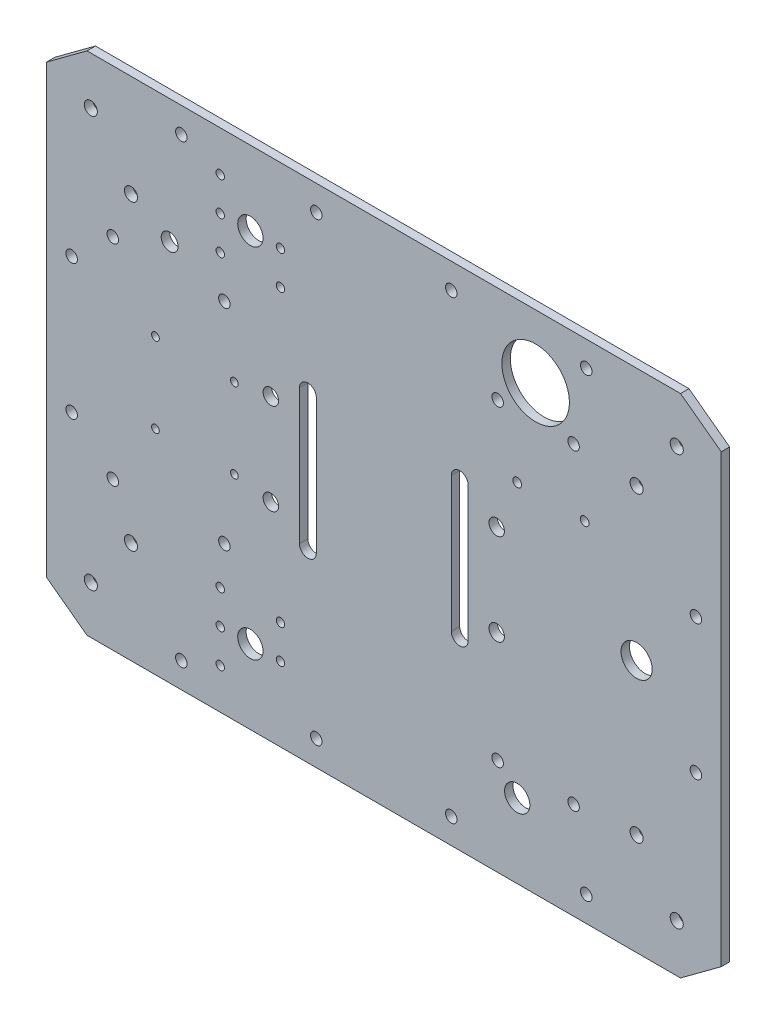
SolidWorks part; units mm, degrees
material "Thornel Mat VMA"
ref_plane "Front Plane" through (0, 0, 0) normal (0, 0, 1) x (1, 0, 0)
ref_plane "Top Plane" through (0, 0, 0) normal (0, 1, 0) x (1, 0, 0)
ref_plane "Right Plane" through (0, 0, 0) normal (1, 0, 0) x (0, 0, -1)
sketch "Sketch1" plane through (0, 0, 0) normal (0, 0, 1) x (1, 0, 0)
  line L0 (-127, 0) -> (127, 0) construction
  line L1 (0, -95.25) -> (0, 95.25) construction
  line L2 (-107.95, 0) -> (-107.95, 41.011) construction
  line L3 (-107.95, 41.011) -> (-95.25, 41.011) construction
  line L4 (-95.25, 41.011) -> (-79.9365, 52.3423) construction
  line L5 (-79.9365, 52.3423) -> (-79.9365, 76.2) construction
  line L6 (-79.9365, 76.2) -> (0, 76.2) construction
  line L7 (-95.25, 41.011) -> (-127, 83.9186) construction
  line L8 (-79.9365, 52.3423) -> (-111.6865, 95.25) construction
  line L9 (-111.6865, -95.25) -> (-127, -83.9186)
  line L10 (111.6865, -95.25) -> (127, -83.9186)
  line L11 (111.6865, 95.25) -> (127, 83.9186)
  line L12 (-87.5933, 46.6767) -> (-95.1475, 56.8856) construction
  line L13 (-95.1475, 56.8856) -> (-110.256, 77.3036) construction
  line L24 (127, -83.9186) -> (127, 83.9186)
  line L26 (111.6865, 95.25) -> (-111.6865, 95.25)
  line L27 (-111.6865, 95.25) -> (-127, 83.9186)
  line L28 (-127, 83.9186) -> (-127, -83.9186)
  line L30 (-111.6865, -95.25) -> (111.6865, -95.25)
  circle A0 centre (-95.1475, 56.8856) radius 2.4638
  circle A1 centre (-110.256, 77.3036) radius 2.4638
  circle A2 centre (110.256, 77.3036) radius 2.4638
  circle A3 centre (95.1475, 56.8856) radius 2.4638
  circle A4 centre (-110.256, -77.3036) radius 2.4638
  circle A5 centre (-95.1475, -56.8856) radius 2.4638
  circle A6 centre (110.256, -77.3036) radius 2.4638
  circle A7 centre (95.1475, -56.8856) radius 2.4638
  circle A8 centre (95.1475, 0) radius 5.855
  point P12 (0, 0)
  dimension "D10" = 11.71
  dimension "D1" = 190.5
  dimension "D2" = 254
  dimension "D3" = 19.05
  dimension "D4" = 19.05
  dimension "D5" = 12.7
  dimension "D6" = 19.05
  dimension "D7" = 143.5
  dimension "D8" = 12.7
  dimension "D9" = 25.4
extrude "Boss-Extrude1" add sketch "Sketch1" along normal blind 3.175
sketch "Sketch2" plane through (0, 0, 3.175) normal (0, 0, 1) x (1, 0, 0)
  line L0 (-127, 0) -> (127, 0) construction
  line L1 (-127, 83.9186) -> (-127, -83.9186) construction
  line L2 (127, -83.9186) -> (127, 83.9186) construction
  line L3 (57.15, 65.0875) -> (57.15, -65.0875) construction
  line L4 (38.1, 65.0875) -> (76.2, 65.0875)
  line L5 (38.1, 65.0875) -> (38.1, -65.0875)
  line L6 (38.1, -65.0875) -> (76.2, -65.0875)
  line L7 (76.2, 65.0875) -> (76.2, -65.0875)
  line L8 (38.1, 65.0875) -> (76.2, -65.0875) construction
  line L9 (38.1, -65.0875) -> (76.2, 65.0875) construction
  line L10 (57.15, 58.7375) -> (47.625, 58.7375) construction
  line L11 (47.625, 58.7375) -> (38.1, 58.7375) construction
  circle A0 centre (42.8625, 58.7375) radius 2.159
  circle A1 centre (42.8625, -58.7375) radius 2.159
  circle A2 centre (71.4375, -58.7375) radius 2.159
  circle A3 centre (71.4375, 58.7375) radius 2.159
  point P6 (57.15, 0)
  point P17 (42.8625, 58.7375)
  dimension "D1" = 38.1
  dimension "D2" = 130.175
  dimension "D3" = 6.35
  dimension "D4" = 9.525
  dimension "D5" = 69.85
extrude "Cut-Extrude1" cut sketch "Sketch2" against normal through all contours A1 | A2 | A3 | A0 region at (42.8625, 58.7375, 3.175) region at (42.8625, -58.7375, 3.175) region at (71.4375, -58.7375, 3.175) region at (71.4375, 58.7375, 3.175)
sketch "Sketch3" plane through (0, 0, 3.175) normal (0, 0, 1) x (1, 0, 0)
  line L0 (0, 95.25) -> (0, -95.25) construction
  line L1 (111.6865, 95.25) -> (-111.6865, 95.25) construction
  line L2 (-111.6865, -95.25) -> (111.6865, -95.25) construction
  line L3 (127, 0) -> (-127, 0) construction
  line L4 (127, -83.9186) -> (127, 83.9186) construction
  line L5 (-127, 83.9186) -> (-127, -83.9186) construction
  line L8 (119.3433, -89.5843) -> (111.789, -79.3753) construction
  line L10 (111.6865, -95.25) -> (127, -83.9186) construction
  line L11 (111.6865, -95.25) -> (127, -83.9186)
  circle A0 centre (111.789, -79.3753) radius 1.9844
  circle A1 centre (96.6805, -58.9574) radius 1.9844
  dimension "D2" = 3.9688
  dimension "D3" = 3.9688
  dimension "D1" = 12.7
  dimension "D4" = 25.4
sketch "Sketch5" plane through (0, 0, 0) normal (0, 0, -1) x (-1, 0, 0)
  line L0 (-127, 0) -> (127, 0) construction
  line L1 (105.9946, 43.5) -> (55.9947, 43.5) construction
  line L2 (105.9946, 43.5) -> (105.9946, -43.5) construction
  line L3 (105.9946, -43.5) -> (55.9947, -43.5) construction
  line L4 (55.9947, 43.5) -> (55.9947, -43.5) construction
  line L5 (89.2369, 18.0341) -> (89.2369, -18.0339)
  line L6 (67.8946, 95.25) -> (67.8946, -95.25) construction
  line L7 (-71.4375, 58.7375) -> (-42.8625, 58.7375) construction
  line L8 (0, 64.0679) -> (0, -49.8393) construction
  line L9 (-42.5, 17.2) -> (42.5, 17.2) construction
  line L10 (-42.5, 17.2) -> (-42.5, -17.2) construction
  line L11 (-42.5, -17.2) -> (42.5, -17.2) construction
  line L12 (42.5, 17.2) -> (42.5, -17.2) construction
  line L13 (-42.5, 17.2) -> (42.5, -17.2) construction
  line L14 (-42.5, -17.2) -> (42.5, 17.2) construction
  line L15 (80.5946, 60.96) -> (31.75, 60.96) construction
  line L16 (61.5446, -67.31) -> (-87.4336, -67.31) construction
  line L17 (50.2154, -67.31) -> (50.2154, 67.31) construction
  line L18 (50.2154, 67.31) -> (38.8861, 67.31) construction
  line L19 (-28.575, 25.4) -> (-28.575, -25.4) construction
  line L20 (-111.6865, 95.25) -> (111.6865, 95.25) construction
  line L21 (-127, -83.9186) -> (-127, 83.9186) construction
  line L22 (-57.15, 71.4375) -> (80.5946, 71.4375) construction
  line L23 (80.5946, 71.4375) -> (80.5946, 48.58) construction
  line L25 (80.5946, -77.0458) -> (80.5946, 48.58) construction
  line L26 (127, 0) -> (-127, 0) construction
  line L27 (80.9947, 0) -> (80.9947, -8419.0368) construction
  line L28 (-25.4, 25.4) -> (-25.4, -25.4)
  line L29 (-31.75, 25.4) -> (-31.75, -25.4)
  line L30 (28.575, 25.4) -> (28.575, -25.4) construction
  line L31 (25.4, 25.4) -> (25.4, -25.4)
  line L32 (31.75, 25.4) -> (31.75, -25.4)
  line L33 (71.0787, 0) -> (71.0787, 12.3782) construction
  line L34 (53.2197, 18.0341) -> (89.2369, 18.0341)
  line L35 (53.2197, 18.0341) -> (53.2197, -18.0339)
  line L36 (53.2197, -18.0339) -> (89.2369, -18.0339)
  line L40 (-57.15, 58.7375) -> (-57.15, 95.25) construction
  circle A0 centre (61.5446, -54.61) radius 1.5875
  circle A1 centre (61.5446, -67.31) radius 1.5875
  circle A2 centre (80.5946, 48.58) radius 3.175
  circle A3 centre (-57.15, 71.4375) radius 12.7
  circle A4 centre (61.5446, 54.61) radius 1.5875
  circle A5 centre (61.5446, -80.01) radius 1.5875
  circle A6 centre (-50.2154, -67.31) radius 4.7625
  circle A7 centre (50.2154, -67.31) radius 4.7625
  circle A8 centre (61.5446, 67.31) radius 1.5875
  circle A9 centre (61.5446, 80.01) radius 1.5875
  circle A10 centre (50.2154, 67.31) radius 4.7625
  circle A11 centre (-50.2154, 35.56) radius 1.651
  circle A12 centre (59.9952, 39.4995) radius 2.159
  circle A13 centre (101.9941, 39.4995) radius 2.159
  circle A14 centre (59.9952, -39.4995) radius 2.159
  circle A15 centre (101.9941, -39.4995) radius 2.159
  circle A16 centre (38.8861, 67.31) radius 1.5875
  circle A17 centre (38.8861, 54.61) radius 1.5875
  circle A18 centre (38.8861, -67.31) radius 1.5875
  circle A19 centre (38.8861, -54.61) radius 1.5875
  arc A20 (-25.4, 25.4) -> (-31.75, 25.4) centre (-28.575, 25.4) ccw
  arc A21 (-31.75, -25.4) -> (-25.4, -25.4) centre (-28.575, -25.4) ccw
  arc A22 (25.4, 25.4) -> (31.75, 25.4) centre (28.575, 25.4) cw
  arc A23 (31.75, -25.4) -> (25.4, -25.4) centre (28.575, -25.4) cw
  circle A24 centre (56.2197, 15.0341) radius 1.4478
  circle A25 centre (56.2197, -15.0341) radius 1.4478
  circle A26 centre (85.9377, -15.0341) radius 1.4478
  circle A27 centre (85.9377, 15.0341) radius 1.4478
  circle A28 centre (-42.5, 17.2) radius 2.9083
  circle A29 centre (-42.5, -17.2) radius 2.9083
  circle A30 centre (42.5, -17.2) radius 2.9083
  circle A31 centre (42.5, 17.2) radius 2.9083
  circle A32 centre (-75.6154, 35.6276) radius 1.651
  point P0 (80.9947, 0)
  point P9 (0, 0)
  point P77 (-28.575, 0)
  point P84 (28.575, 0)
  point P89 (71.0787, 0)
  point P112 (0, 0)
  dimension "D10" = 6.35
  dimension "D15" = 2.9997
  dimension "D17" = 3.302
  dimension "D18" = 3.302
  dimension "D25" = 4.0005
  dimension "D45" = 2.8956
  dimension "D9" = 59.69
  dimension "D13" = 14.859
  dimension "D14" = 3
  dimension "D8" = 111.76
  dimension "D1" = 87.0001
  dimension "D2" = 49.9999
  dimension "D4" = 34.4
  dimension "D5" = 85
  dimension "D6" = 6.35
  dimension "D7" = 12.7
  dimension "D11" = 5.08
  dimension "D12" = 25.4
  dimension "D16" = 25.4
  dimension "D26" = 4.0005
  dimension "D38" = 50.8
  dimension "D39" = 6.35
  dimension "D40" = 28.575
  dimension "D41" = 36.0172
  dimension "D42" = 36.068
  dimension "D44" = 3
extrude "Cut-Extrude2" cut sketch "Sketch5" against normal through all contours A3 | A2 | A14 | A15 | A13 | A12 | L29 A21 L28 A20 | A23 L4 A22 L31 | A23 L32 A22 L4 | A27 | A24 | A25 | A26
sketch "Sketch6" plane through (0, 0, 0) normal (0, 0, -1) x (-1, 0, 0)
  line L0 (0, 0) -> (-135.1326, 0) construction
  line L1 (0, 0) -> (0, -95.25) construction
  line L2 (111.6865, -95.25) -> (-111.6865, -95.25) construction
  line L3 (-76.2, -95.25) -> (-76.2, -85.725) construction
  line L4 (117.475, 0) -> (117.475, -25.4) construction
  line L5 (127, 0) -> (-127, 0) construction
  line L6 (127, 83.9186) -> (127, -83.9186) construction
  circle A0 centre (-76.2, -85.725) radius 2.159
  circle A1 centre (-25.4, -85.725) radius 2.159
  circle A2 centre (25.4, -85.725) radius 2.159
  circle A3 centre (76.2, -85.725) radius 2.159
  circle A4 centre (76.2, 85.725) radius 2.159
  circle A5 centre (25.4, 85.725) radius 2.159
  circle A6 centre (-25.4, 85.725) radius 2.159
  circle A7 centre (-76.2, 85.725) radius 2.159
  circle A8 centre (117.475, -25.4) radius 2.159
  circle A9 centre (117.475, 25.4) radius 2.159
  circle A10 centre (-117.475, 25.4) radius 2.159
  circle A11 centre (-117.475, -25.4) radius 2.159
  dimension "D2" = 9.525
  dimension "D3" = 76.2
  dimension "D5" = 9.525
  dimension "D6" = 25.4
  dimension "D4" = 4
extrude "Cut-Extrude3" cut sketch "Sketch6" against normal through all
extrude "Cut-Extrude4" cut sketch "Sketch5<3>" against normal through all contours A28 | A29 | A31 | A30
sketch "Sketch5<3>" plane through (0, 0, 0) normal (0, 0, -1) x (-1, 0, 0) same geometry as "Sketch5"
extrude "Cut-Extrude5" cut sketch "Sketch5<4>" against normal through all contours A10 | A9 | A8 | A4 | A0 | A1 | A5 | A7 | A6
sketch "Sketch5<4>" plane through (0, 0, 0) normal (0, 0, -1) x (-1, 0, 0) same geometry as "Sketch5"
extrude "Cut-Extrude6" cut sketch "Sketch5<5>" against normal blind 2.54 contours A18 | A17 | A16
sketch "Sketch5<5>" plane through (0, 0, 0) normal (0, 0, -1) x (-1, 0, 0) same geometry as "Sketch5"
extrude "Cut-Extrude7" cut sketch "Sketch5<6>" against normal through all contours A17 | A18 | A16
sketch "Sketch5<6>" plane through (0, 0, 0) normal (0, 0, -1) x (-1, 0, 0) same geometry as "Sketch5"
sketch "Sketch8" plane through (0, 0, 3.175) normal (0, 0, 1) x (1, 0, 0)
extrude "Cut-Extrude8" cut sketch "Sketch5<7>" against normal blind 2.54 contours A11
sketch "Sketch5<7>" plane through (0, 0, 0) normal (0, 0, -1) x (-1, 0, 0) same geometry as "Sketch5"
extrude "Cut-Extrude9" cut sketch "Sketch5<9>" against normal blind 2.54 contours A11 | A32
sketch "Sketch5<9>" plane through (0, 0, 0) normal (0, 0, -1) x (-1, 0, 0) same geometry as "Sketch5"
extrude "Cut-Extrude13" cut sketch "Sketch5<12>" against normal through all both and the other way through all contours A11 | A32
sketch "Sketch5<12>" plane through (0, 0, 0) normal (0, 0, -1) x (-1, 0, 0) same geometry as "Sketch5"
extrude "Cut-Extrude14" cut sketch "Sketch5<13>" against normal through all contours A19
sketch "Sketch5<13>" plane through (0, 0, 0) normal (0, 0, -1) x (-1, 0, 0) same geometry as "Sketch5"
